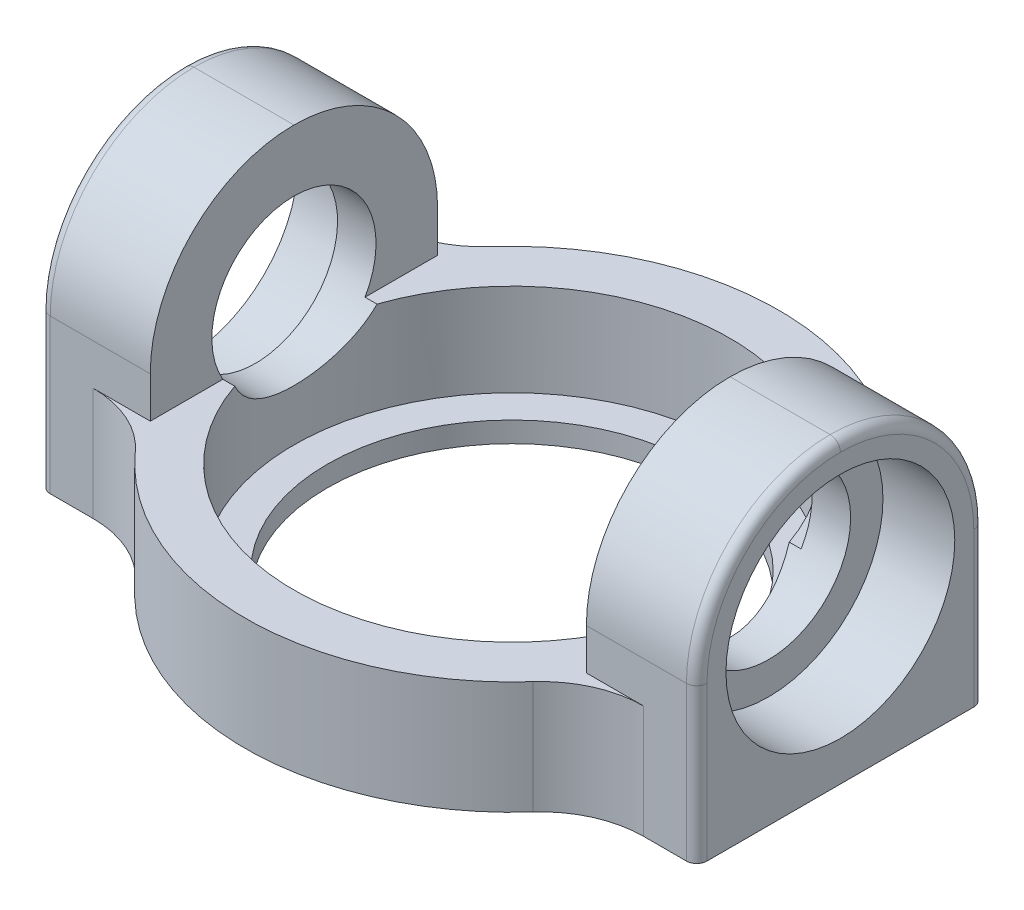
SolidWorks part; units mm, degrees
ref_plane "Front Plane" through (0, 0, 0) normal (0, 0, 1) x (1, 0, 0)
ref_plane "Top Plane" through (0, 0, 0) normal (0, 1, 0) x (1, 0, 0)
ref_plane "Right Plane" through (0, 0, 0) normal (1, 0, 0) x (0, 0, -1)
sketch "Sketch1" plane through (0, 0, 0) normal (0, 1, 0) x (1, 0, 0)
  circle A0 centre (0, 0) radius 21.25
  circle A1 centre (0, 0) radius 26
  dimension "D1" = 42.5
  dimension "D2" = 52
extrude "Boss-Extrude1" add sketch "Sketch1" along normal blind 9
sketch "Sketch2" plane through (0, 0, 0) normal (0, -1, 0) x (1, 0, 0)
  circle A0 centre (0, 0) radius 18
  circle A1 centre (0, 0) radius 26 construction
  circle A2 centre (0, 0) radius 26
  dimension "D1" = 36
extrude "Boss-Extrude2" add sketch "Sketch2" along normal blind 2
sketch "Sketch3" plane through (0, 9, 0) normal (0, 1, 0) x (1, 0, 0)
  line L0 (0, 0) -> (26.625, 0) construction
  line L1 (0, 0) -> (-26.625, 0) construction
  line L3 (21.25, 14) -> (32, 14)
  line L4 (21.25, 14) -> (21.25, -14)
  line L5 (21.25, -14) -> (32, -14)
  line L6 (32, 14) -> (32, -14)
  line L7 (21.25, 14) -> (32, -14) construction
  line L8 (21.25, -14) -> (32, 14) construction
  line L9 (-32, 14) -> (-21.25, 14)
  line L10 (-32, 14) -> (-32, -14)
  line L11 (-32, -14) -> (-21.25, -14)
  line L12 (-21.25, 14) -> (-21.25, -14)
  line L13 (-32, 14) -> (-21.25, -14) construction
  line L14 (-32, -14) -> (-21.25, 14) construction
  circle A1 centre (0, 0) radius 21.25 construction
  point P12 (21.4994, -12.7583)
  point P15 (31.5419, 12.3627)
  point P16 (-21.6506, -12.5)
  point P17 (21.9089, -14)
  point P18 (-21.9089, -14)
  point P19 (0, 0)
  dimension "D1" = 28
  dimension "D2" = 32
extrude "Boss-Extrude3" add sketch "Sketch3" against normal up to surface (11 mm away) and the other way blind 18 up to face at (0, -2, -26)
sketch "Sketch4" plane through (32, 0, 0) normal (1, 0, 0) x (0, 0, -1)
  line L0 (0, -2) -> (0, 13) construction
  line L1 (-14, -2) -> (14, -2) construction
  circle A0 centre (0, 13) radius 11.15
  point P5 (0, 10.7672)
  dimension "D1" = 22.3
  dimension "D2" = 15
extrude "Cut-Extrude1" cut sketch "Sketch4" against normal blind 7 contours A0
sketch "Sketch5" plane through (-32, 0, 0) normal (-1, 0, 0) x (0, 0, 1)
  circle A0 centre (0, 13) radius 11.15 construction
  circle A1 centre (0, 13) radius 11.15
extrude "Cut-Extrude2" cut sketch "Sketch5" against normal blind 7
sketch "Sketch6" plane through (25, 0, 0) normal (1, 0, 0) x (0, 0, -1)
  circle A0 centre (0, 13) radius 8
  circle A1 centre (0, 13) radius 11.15 construction
  dimension "D1" = 16
extrude "Cut-Extrude3" cut sketch "Sketch6" against normal through all
fillet "Fillet2" radius 14 4 edges at (-26.625, 27, 14) (-26.625, 27, -14) (26.625, 27, -14) (26.625, 27, 14)
fillet "Fillet3" radius 10 4 edges at (-21.9089, 3.5, 14) (21.9089, 3.5, 14) (-21.9089, 3.5, -14) (21.9089, 3.5, -14)
fillet "Fillet4" radius 1 8 edges at (-32, 5.5, -14) (-32, 22.8995, -9.8995) (-32, 22.8995, 9.8995) (32, 5.5, -14) (32, 22.8995, -9.8995) (32, 22.8995, 9.8995) (-32, 5.5, 14) (32, 5.5, 14)
